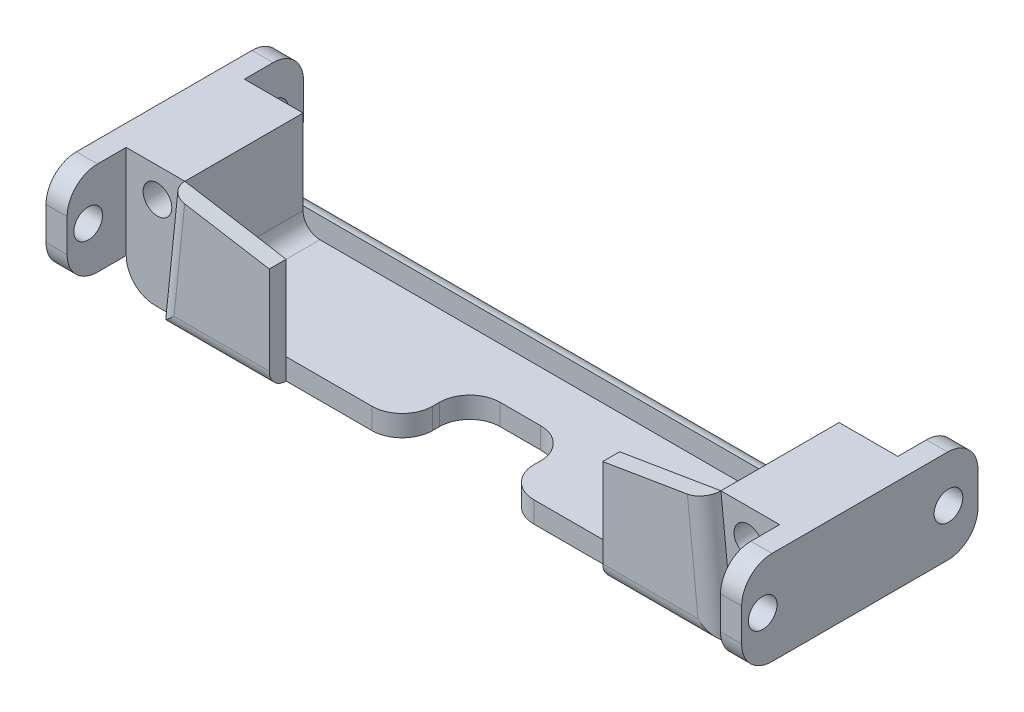
SolidWorks part; units mm, degrees
ref_plane "前视基准面" through (0, 0, 0) normal (0, 0, 1) x (1, 0, 0)
ref_plane "上视基准面" through (0, 0, 0) normal (0, 1, 0) x (1, 0, 0)
ref_plane "右视基准面" through (0, 0, 0) normal (1, 0, 0) x (0, 0, -1)
other "Configuration Table"
sketch "草图1" plane through (0, 0, 0) normal (0, 0, 1) x (1, 0, 0)
  line L0 (0, 0) -> (-31.75, 0) construction
  line L1 (-31.75, 0) -> (31.75, 0) construction
  line L2 (-31.75, 0) -> (-31.75, 12) construction
  line L3 (-31.75, 12) -> (31.75, 12) construction
  line L4 (31.75, 12) -> (39.75, 12) construction
  line L5 (39.75, 12) -> (39.75, 0) construction
  line L6 (39.75, 0) -> (39.75, -2.5) construction
  line L7 (39.75, -2.5) -> (-31.75, -2.5) construction
  line L8 (-31.75, -2.5) -> (-39.75, -2.5) construction
  line L9 (-39.75, -2.5) -> (-39.75, 12) construction
  line L10 (-39.75, 12) -> (-31.75, 12)
  line L11 (-31.75, 12) -> (-31.75, 0)
  line L12 (-31.75, 0) -> (31.75, 0)
  line L13 (31.75, 0) -> (31.75, 12)
  line L14 (31.75, 12) -> (39.75, 12)
  line L15 (39.75, 12) -> (39.75, -2.5)
  line L16 (39.75, -2.5) -> (-39.75, -2.5)
  line L17 (-39.75, -2.5) -> (-39.75, 12)
  dimension "D1" = 31.75
  dimension "D2" = 63.5
  dimension "D3" = 12
  dimension "D4" = 8
  dimension "D5" = 2.5
  dimension "D6" = 8
extrude "凸台-拉伸1" add sketch "草图1" along normal blind 14
sketch "草图2" plane through (0, 0, 14) normal (0, 0, 1) x (1, 0, 0)
  line L0 (0, 0) -> (-35, 0) construction
  line L1 (31.75, 0) -> (-31.75, 0) construction
  line L2 (-35, 0) -> (35, 0) construction
  line L3 (-35, 0) -> (-35, 12) construction
  line L4 (-31.75, 12) -> (-39.75, 12) construction
  line L5 (35, 0) -> (35, 12) construction
  line L6 (39.75, 12) -> (31.75, 12) construction
  line L7 (-35, 0) -> (-35, 8) construction
  line L8 (35, 0) -> (35, 8) construction
  line L10 (-39.75, 12) -> (-38.7, 12)
  line L11 (-39.75, 12) -> (-39.75, -2.5)
  line L12 (-39.75, -2.5) -> (-38.7, -2.5)
  line L13 (-38.7, 12) -> (-38.7, -2.5)
  line L14 (-39.75, -2.5) -> (39.75, -2.5) construction
  line L16 (39.75, 12) -> (38.7, 12)
  line L17 (39.75, 12) -> (39.75, -2.5)
  line L18 (39.75, -2.5) -> (38.7, -2.5)
  line L19 (38.7, 12) -> (38.7, -2.5)
  circle A0 centre (-35, 8) radius 1.7
  circle A1 centre (35, 8) radius 1.7
  dimension "D5" = 3.4
  dimension "D6" = 3.4
  dimension "D1" = 35
  dimension "D2" = 70
  dimension "D3" = 8
  dimension "D4" = 8
  dimension "D7" = 14.5
  dimension "D8" = 1.05
  dimension "D9" = 14.5
  dimension "D10" = 1.05
extrude "切除-拉伸1" cut sketch "草图2" against normal up to surface (14 mm away) up to face at (0, 5.375, 0)
fillet "圆角1" radius 2 2 edges at (31.75, 0, 7) (-31.75, 0, 7)
fillet "圆角2" radius 3.4 2 edges at (38.7, -2.5, 7) (-38.7, -2.5, 7)
sketch "草图3" plane through (0, 0, 14) normal (0, 0, 1) x (1, 0, 0)
  line L0 (-31.75, 12) -> (-31.75, -2.5) construction
  line L1 (-35.3, -2.5) -> (35.3, -2.5) construction
  line L2 (31.75, 12) -> (31.75, -2.5) construction
  line L3 (-31.75, -2.5) -> (-33.25, -2.5) construction
  line L4 (31.75, -2.5) -> (33.25, -2.5) construction
  line L5 (-31.75, 12) -> (-33.25, -2.5)
  line L6 (-33.25, -2.5) -> (-31.75, -2.5)
  line L7 (-31.75, -2.5) -> (-19.75, -2.5)
  line L8 (-19.75, -2.5) -> (-19.75, 0)
  line L9 (29.75, 0) -> (-29.75, 0) construction
  line L10 (-19.75, 0) -> (-19.75, 10)
  line L11 (-19.75, 10) -> (-31.75, 12)
  line L12 (31.75, 12) -> (33.25, -2.5)
  line L13 (33.25, -2.5) -> (31.75, -2.5)
  line L14 (31.75, -2.5) -> (19.75, -2.5)
  line L15 (19.75, -2.5) -> (19.75, 0)
  line L16 (19.75, 0) -> (19.75, 10)
  line L17 (19.75, 10) -> (31.75, 12)
  dimension "D1" = 1.5
  dimension "D2" = 1.5
  dimension "D3" = 12
  dimension "D4" = 10
  dimension "D5" = 12
  dimension "D6" = 10
extrude "凸台-拉伸6" add sketch "草图3" along normal blind 2
sketch "草图4" plane through (0, 0, 0) normal (0, 0, -1) x (-1, 0, 0)
  line L0 (-29.75, 0) -> (-29.75, -2.5) construction
  line L1 (35.3, -2.5) -> (-35.3, -2.5) construction
  line L2 (-29.75, 0) -> (-35.3, 0) construction
  line L3 (-35.3, 0) -> (-35.3, 2.5) construction
  line L4 (-35.3, 2.5) -> (31.75, 2.5) construction
  line L5 (31.75, 2) -> (31.75, 12) construction
  line L6 (31.75, 2.5) -> (35, 2.5) construction
  line L7 (35, 2.5) -> (35, -1.25) construction
  line L8 (35, -1.25) -> (35, -2.5) construction
  line L9 (35, -2.5) -> (-35.3, -2.5) construction
  line L10 (-35.3, -2.5) -> (-35.3, 0) construction
  line L12 (-35.3, 2.5) -> (35, 2.5)
  line L13 (-35.3, 2.5) -> (-35.3, -2.5)
  line L14 (-35.3, -2.5) -> (35, -2.5)
  line L15 (35, 2.5) -> (35, -2.5)
  dimension "D1" = 2.5
extrude "凸台-拉伸7" add sketch "草图4" along normal blind 2
fillet "圆角5" radius 2 7 edges at (0.15, 2.5, -2) (-26.5, -2.5, 16) (26.5, -2.5, 16) (32.5, 4.75, 16) (-32.5, 4.75, 16) (-35, 0, -2) (35.3, 0, -2)
fillet "圆角6" radius 2 2 edges at (-35, 0, 0) (35.3, 0, 0)
sketch "草图5" plane through (0, 0, 0) normal (0, 0, -1) x (-1, 0, 0)
  line L0 (-28.3796, 0) -> (-40.502, 0) construction
  line L1 (-29.75, 0) -> (29.75, 0) construction
  line L2 (-35, 6.3) -> (-35, 0) construction
  line L3 (-35, 0) -> (-35, 8) construction
  line L4 (-35, 8) -> (-35, 8.5) construction
  line L5 (-40.502, 0) -> (42.5027, 0) construction
  line L6 (35, 6.3) -> (35, 0) construction
  line L7 (35, 0) -> (35, 8) construction
  line L8 (35, 8) -> (35, 8.5) construction
  circle A0 centre (-35, 8) radius 1.7 construction
  circle A1 centre (35, 8) radius 1.7 construction
  circle A2 centre (-35, 8) radius 2.1645
  circle A3 centre (35, 8) radius 2.3376
  dimension "D1" = 0.5
  dimension "D2" = 0.5
extrude "凸台-拉伸8" add sketch "草图5" against normal up to surface (14 mm away) up to face at (-35.6808, 3.8392, 14)
sketch "草图6" plane through (0, 0, 0) normal (0, 0, -1) x (-1, 0, 0)
  line L0 (-28.7454, 0) -> (-49.0953, 0) construction
  line L1 (-29.75, 0) -> (29.75, 0) construction
  line L2 (0, 0) -> (-35, 0) construction
  line L3 (0, 0) -> (35, 0) construction
  line L4 (35, 0) -> (35, 8.5) construction
  line L5 (-35, 0) -> (-35, 8.5) construction
  circle A0 centre (-35, 8.5) radius 1.7
  circle A1 centre (35, 8.5) radius 1.7
  dimension "D5" = 3.4
  dimension "D6" = 3.4
  dimension "D1" = 35
  dimension "D2" = 35
  dimension "D3" = 8.5
  dimension "D4" = 8.5
extrude "切除-拉伸2" cut sketch "草图6" against normal up to surface (14 mm away) up to face at (0, -1.25, 14)
sketch "草图7" plane through (0, -2.5, 0) normal (0, -1, 0) x (1, 0, 0)
  line L0 (0, 0) -> (0, 14) construction
  line L1 (-19.75, 14) -> (19.75, 14) construction
  line L2 (0, 14) -> (0, 6) construction
  line L3 (0, 6) -> (-6, 6) construction
  line L4 (-6, 6) -> (-6, 14) construction
  line L5 (-6, 14) -> (6, 14) construction
  line L6 (6, 14) -> (6, 6) construction
  line L8 (-6, 14) -> (6, 14)
  line L9 (-6, 14) -> (-6, 6)
  line L10 (-6, 6) -> (6, 6)
  line L11 (6, 14) -> (6, 6)
  dimension "D1" = 8
  dimension "D2" = 6
  dimension "D3" = 12
extrude "切除-拉伸3" cut sketch "草图7" against normal blind 10
fillet "圆角7" radius 3.6 4 edges at (-6, -1.25, 14) (6, -1.25, 14) (-6, -1.25, 6) (6, -1.25, 6)
sketch "草图8" plane through (0, 0, 0) normal (0, 0, -1) x (-1, 0, 0)
  line L0 (-35, 8.5) -> (35, 8.5) construction
  line L1 (-38.7, 12) -> (38.7, 12) construction
sketch "草图9" plane through (38.7, 0, 0) normal (1, 0, 0) x (0, 0, -1)
  line L0 (-14, 12) -> (0, 0.9) construction
  line L1 (-14, 0.9) -> (0, 0.9) construction
  line L2 (0, -2.1686) -> (0, 0.9) construction
  line L3 (-21, 12) -> (-21, 0.9) construction
  line L4 (-21, 12) -> (7, 12)
  line L5 (-21, 12) -> (-21, 0.9)
  line L6 (-21, 0.9) -> (7, 0.9)
  line L7 (7, 12) -> (7, 0.9)
  line L8 (-21, 12) -> (7, 0.9) construction
  line L9 (-21, 0.9) -> (7, 12) construction
  line L10 (-21, 6.45) -> (-16, 6.45) construction
  line L11 (-16, -0.5) -> (-16, 11.6706) construction
  line L12 (-16, 6.45) -> (-18.5, 6.45) construction
  line L13 (7, 12) -> (7, 0.9) construction
  line L14 (7, 6.45) -> (0, 6.45) construction
  line L15 (0, 0.9) -> (0, 12) construction
  line L16 (0, 6.45) -> (3.5, 6.45) construction
  circle A0 centre (-18.5, 6.45) radius 1.7
  circle A1 centre (3.5, 6.45) radius 1.7
  point P7 (-7, 6.45)
  dimension "D3" = 3.4
  dimension "D4" = 3.4
  dimension "D1" = 11.1
  dimension "D2" = 28
extrude "凸台-拉伸9" add sketch "草图9" along normal blind 2.5
sketch "草图10" plane through (-38.7, 0, 0) normal (-1, 0, 0) x (0, 0, 1)
  line L1 (-7, 12) -> (21, 12)
  line L2 (-7, 12) -> (-7, 0.9)
  line L3 (-7, 0.9) -> (21, 0.9)
  line L4 (21, 12) -> (21, 0.9)
  circle A0 centre (18.5, 6.45) radius 1.7
  circle A1 centre (-3.5, 6.45) radius 1.7
extrude "凸台-拉伸10" add sketch "草图10" along normal blind 2.5
fillet "圆角8" radius 3.6 8 edges at (39.95, 0.9, -7) (39.95, 12, -7) (39.95, 0.9, 21) (39.95, 12, 21) (-39.95, 0.9, 21) (-39.95, 12, 21) (-39.95, 0.9, -7) (-39.95, 12, -7)
sketch "草图11" plane through (-41.2, 0, 0) normal (-1, 0, 0) x (0, 0, 1)
  line L0 (-5.2, 6.45) -> (16.8, 6.45) construction
  circle A0 centre (-3.5, 6.45) radius 1.7 construction
  circle A1 centre (18.5, 6.45) radius 1.7 construction
